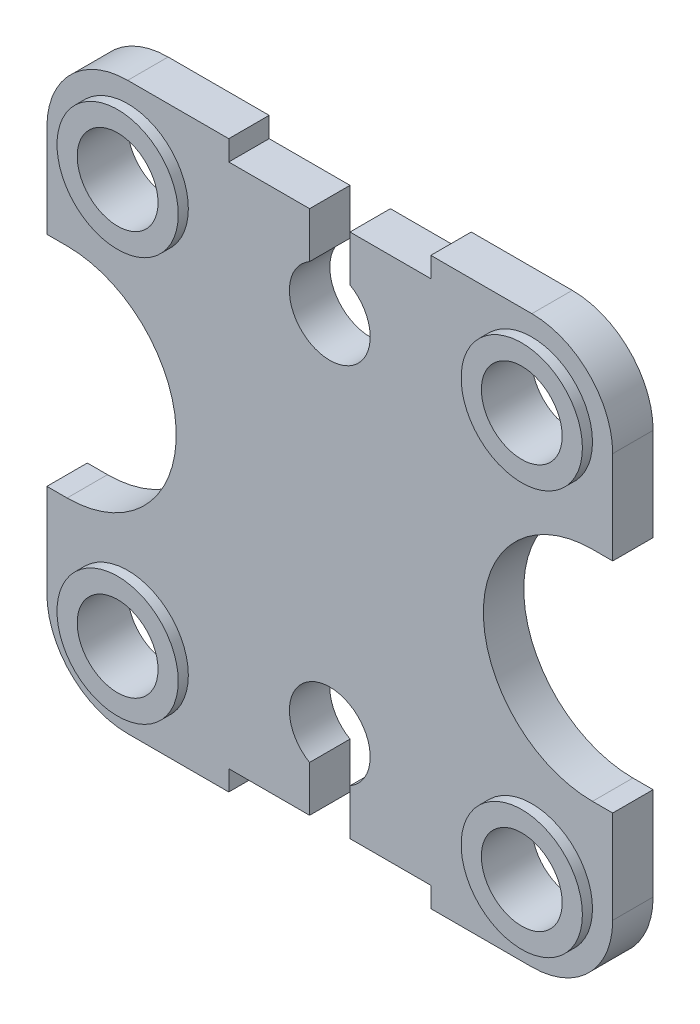
SolidWorks part; units mm, degrees
ref_plane "Front Plane" through (0, 0, 0) normal (0, 0, 1) x (1, 0, 0)
ref_plane "Top Plane" through (0, 0, 0) normal (0, 1, 0) x (1, 0, 0)
ref_plane "Right Plane" through (0, 0, 0) normal (1, 0, 0) x (0, 0, -1)
sketch "Sketch2" plane through (0, 0, 0) normal (0, 0, 1) x (1, 0, 0)
  line L0 (37.355, 312.6417) -> (37.355, -42.354) construction
  line L1 (37.355, 2.2224) -> (87.355, 2.2224)
  line L2 (-2.645, 42.2224) -> (-2.645, 88.2224)
  line L3 (37.355, 282.2224) -> (87.355, 282.2224)
  line L4 (277.355, 42.2224) -> (277.355, 88.2224)
  line L5 (237.355, 312.6417) -> (237.355, -42.354) construction
  line L6 (-60.1778, 242.2224) -> (331.042, 242.2224) construction
  line L7 (87.355, 272.2224) -> (87.355, 282.2224)
  line L8 (331.042, 142.2224) -> (-60.1778, 142.2224) construction
  line L9 (7.355, 196.2224) -> (-2.645, 196.2224)
  line L10 (-60.1778, 42.2224) -> (331.042, 42.2224) construction
  line L11 (7.355, 88.2224) -> (-2.645, 88.2224)
  line L12 (-2.645, 196.2224) -> (-2.645, 242.2224)
  line L13 (137.355, 381.0989) -> (137.355, -76.6121) construction
  line L14 (267.355, 88.2224) -> (277.355, 88.2224)
  line L15 (267.355, 196.2224) -> (277.355, 196.2224)
  line L16 (277.355, 196.2224) -> (277.355, 242.2224)
  line L17 (87.355, 12.2224) -> (127.355, 12.2224)
  line L18 (87.355, 12.2224) -> (87.355, 2.2224)
  line L20 (187.355, 12.2224) -> (187.355, 2.2224)
  line L21 (187.355, 272.2224) -> (187.355, 282.2224)
  line L22 (87.355, 272.2224) -> (127.355, 272.2224)
  line L23 (102.0325, 52.2224) -> (172.9964, 52.2224) construction
  line L28 (102.0325, 232.2224) -> (172.9964, 232.2224) construction
  line L29 (127.355, 272.2224) -> (127.355, 249.543)
  line L32 (127.355, 12.2224) -> (127.355, 34.9019)
  line L34 (147.355, 34.9019) -> (147.355, 12.2224)
  line L37 (147.355, 249.543) -> (147.355, 272.2224)
  line L38 (147.355, 272.2224) -> (187.355, 272.2224)
  line L39 (147.355, 12.2224) -> (187.355, 12.2224)
  line L40 (187.355, 2.2224) -> (237.355, 2.2224)
  line L41 (187.355, 282.2224) -> (237.355, 282.2224)
  circle A0 centre (37.355, 242.2224) radius 30
  circle A1 centre (37.355, 242.2224) radius 20
  circle A2 centre (37.355, 42.2224) radius 20
  circle A3 centre (37.355, 42.2224) radius 30
  circle A4 centre (237.355, 42.2224) radius 20
  circle A5 centre (237.355, 42.2224) radius 30
  circle A6 centre (237.355, 242.2224) radius 20
  circle A7 centre (237.355, 242.2224) radius 30
  arc A8 (37.355, 282.2224) -> (-2.645, 242.2224) centre (37.355, 242.2224) ccw
  arc A9 (277.355, 242.2224) -> (237.355, 282.2224) centre (237.355, 242.2224) ccw
  arc A10 (277.355, 42.2224) -> (237.355, 2.2224) centre (237.355, 42.2224) cw
  arc A11 (37.355, 2.2224) -> (-2.645, 42.2224) centre (37.355, 42.2224) cw
  arc A12 (7.355, 88.2224) -> (7.355, 196.2224) centre (7.355, 142.2224) ccw
  arc A13 (267.355, 88.2224) -> (267.355, 196.2224) centre (267.355, 142.2224) cw
  arc A14 (147.355, 34.9019) -> (127.355, 34.9019) centre (137.355, 52.2224) ccw
  arc A15 (147.355, 249.543) -> (127.355, 249.543) centre (137.355, 232.2224) cw
  point P62 (129.632, 249.7923)
  dimension "D4" = 60
  dimension "D7" = 40
  dimension "D8" = 40
  dimension "D2" = 10
  dimension "D1" = 100
  dimension "D3" = 200
  dimension "D5" = 100
  dimension "D9" = 180
extrude "Boss-Extrude2" add sketch "Sketch2" along normal blind 20 contours L37 A15 L29 L22 L7 L3 A8 L12 L9 A12 L11 L2 A11 L1 L18 L17 L32 A14 L34 L39 L20 L40 A10 L4 L14 A13 L15 L16 A9 L41 L21 L38 A7 A3 A0 A5 region at (137.355, 142.2224, 0)
extrude "Boss-Extrude3" add sketch "Sketch2<5>" along normal blind 25 contours A0 A1 | A7 A6 | A3 A2 | A5 A4 region at (8.2035, 242.2224, 0) region at (8.2035, 42.2224, 0) region at (208.2035, 42.2224, 0) region at (208.2035, 242.2224, 0)
sketch "Sketch2<5>" plane through (0, 0, 0) normal (0, 0, 1) x (1, 0, 0) same geometry as "Sketch2"
